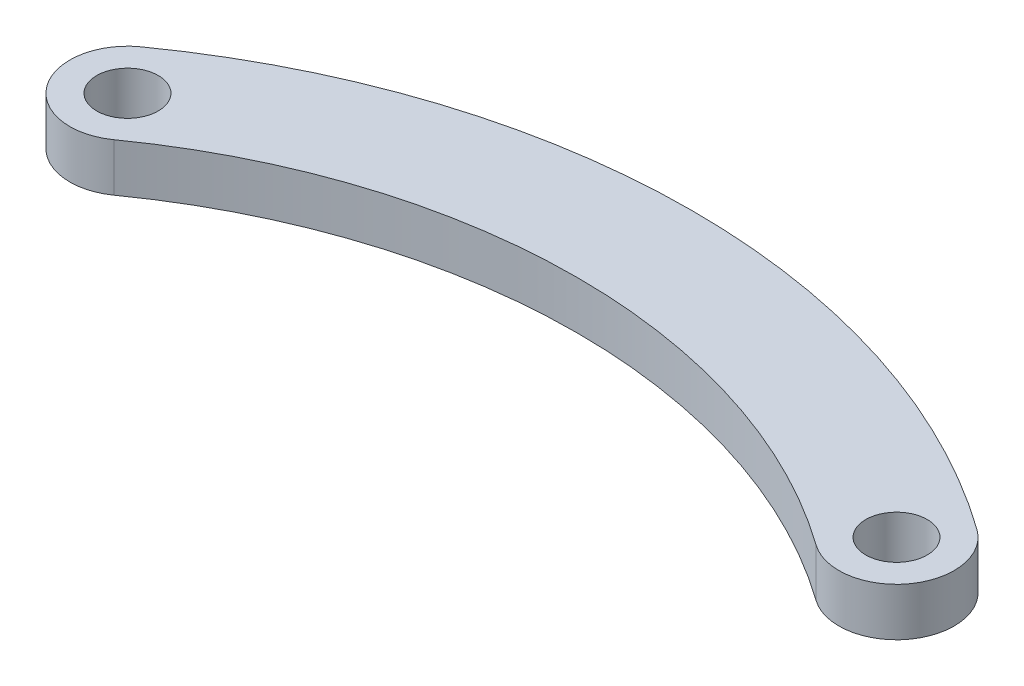
SolidWorks part; units mm, degrees
material "碳纤维"
ref_plane "前视基准面" through (0, 0, 0) normal (0, 0, 1) x (1, 0, 0)
ref_plane "上视基准面" through (0, 0, 0) normal (0, 1, 0) x (1, 0, 0)
ref_plane "右视基准面" through (0, 0, 0) normal (1, 0, 0) x (0, 0, -1)
other "Configuration Table"
ref_axis "基准轴1" through (-66.99, 0, 0) along (1, 0, 0)
ref_axis "基准轴2" through (0, 56.25, 0) along (0, -1, 0)
ref_axis "基准轴3" through (0, 0, -92.9589) along (0, 0, 1)
sketch "草图1" plane through (0, 0, 0) normal (0, 1, 0) x (1, 0, 0)
  line L0 (0, 0) -> (40, 0) construction
  circle A2 centre (0, 0) radius 1.6
  circle A3 centre (40, 0) radius 1.6
  arc A8 (0, 0) -> (40, 0) centre (20, -28.0571) cw construction
  arc A9 (41.7414, 2.4429) -> (-1.7414, 2.4429) centre (20, -28.0571) ccw
  arc A10 (38.2586, -2.4429) -> (1.7414, -2.4429) centre (20, -28.0571) ccw
  arc A11 (38.2586, -2.4429) -> (41.7414, 2.4429) centre (40, 0) ccw
  arc A12 (-1.7414, 2.4429) -> (1.7414, -2.4429) centre (0, 0) ccw
  point P1 (20, 6.3987)
  dimension "D1" = 1.6
  dimension "D2" = 3
  dimension "D3" = 40
extrude "凸台-拉伸1" add sketch "草图1" along normal blind 2.5
